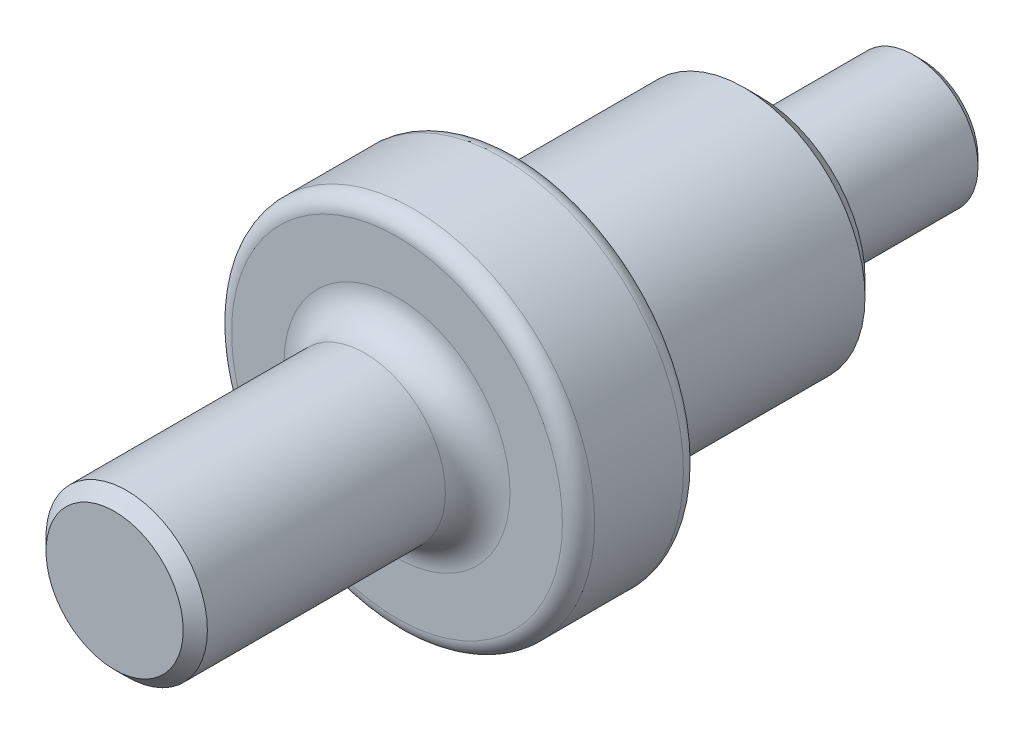
SolidWorks part; units mm, degrees
material "AISI 316 Chapa de aço inoxidável (SS)"
ref_plane "Plano frontal" through (0, 0, 0) normal (0, 0, 1) x (1, 0, 0)
ref_plane "Plano superior" through (0, 0, 0) normal (0, 1, 0) x (1, 0, 0)
ref_plane "Plano direito" through (0, 0, 0) normal (1, 0, 0) x (0, 0, -1)
sketch "Esboço1" plane through (0, 0, 0) normal (0, 0, 1) x (1, 0, 0)
  circle A0 centre (0, 0) radius 8
  dimension "D1" = 16
extrude "Ressalto-extrusão1" add sketch "Esboço1" along normal blind 20
sketch "Esboço2" plane through (0, 0, 20) normal (0, 0, 1) x (1, 0, 0)
  circle A0 centre (0, 0) radius 15
  dimension "D1" = 30
extrude "Ressalto-extrusão2" add sketch "Esboço2" along normal blind 30
sketch "Esboço3" plane through (0, 0, 50) normal (0, 0, 1) x (1, 0, 0)
  circle A0 centre (0, 0) radius 22.5
  dimension "D1" = 45
extrude "Ressalto-extrusão3" add sketch "Esboço3" along normal blind 15
sketch "Esboço4" plane through (0, 0, 65) normal (0, 0, 1) x (1, 0, 0)
  circle A0 centre (0, 0) radius 10
  dimension "D1" = 20
extrude "Ressalto-extrusão4" add sketch "Esboço4" along normal blind 35
chamfer "Chanfro1" distance 1 angle 45 1 edges at (8, 0, 0)
chamfer "Chanfro2" distance 2 angle 45 1 edges at (15, 0, 20)
chamfer "Chanfro3" distance 1.5 angle 45 1 edges at (10, 0, 100)
fillet "Filete1" radius 2 1 edges at (22.5, 0, 50)
fillet "Filete2" radius 2 1 edges at (22.5, 0, 65)
fillet "Filete3" radius 4 1 edges at (10, 0, 65)
